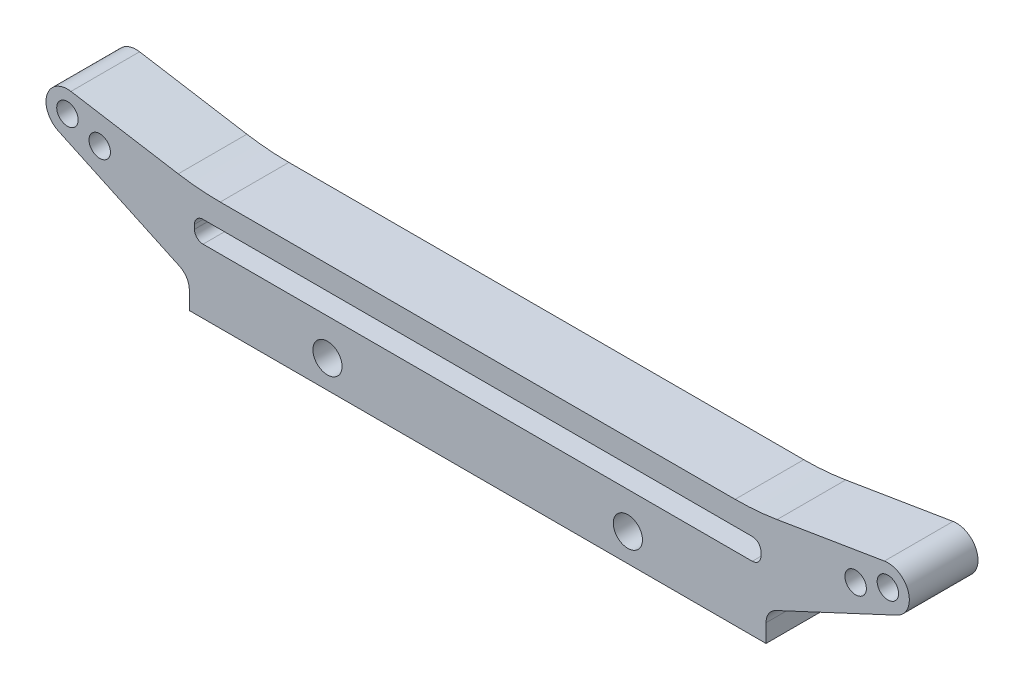
SolidWorks part; units mm, degrees
ref_plane "Front Plane" through (0, 0, 0) normal (0, 0, 1) x (1, 0, 0)
ref_plane "Top Plane" through (0, 0, 0) normal (0, 1, 0) x (1, 0, 0)
ref_plane "Right Plane" through (0, 0, 0) normal (1, 0, 0) x (0, 0, -1)
sketch "Sketch1" plane through (0, 0, 0) normal (0, 0, 1) x (1, 0, 0)
  line L0 (-33.6, 0) -> (33.6, 0)
  line L1 (-34.7548, 4.1585) -> (-48.8565, 10.7342)
  line L2 (-47.3925, 15.4666) -> (-34.8896, 13.4011)
  line L3 (33, 8.75) -> (33, 9.25)
  line L4 (0, -1.6163) -> (0, 13) construction
  line L5 (32, 7.75) -> (-32, 7.75)
  line L6 (47.3925, 15.4666) -> (34.8896, 13.4011)
  line L7 (-32, 10.25) -> (32, 10.25)
  line L8 (-30, 13) -> (30, 13)
  line L9 (-33, 8.75) -> (-33, 9.25)
  line L10 (34.7548, 4.1585) -> (48.8565, 10.7342)
  line L11 (-47.8, 13) -> (-36.9266, 9.0424) construction
  line L12 (-33.6, 0) -> (-33.6, 2.3458)
  line L13 (33.6, 0) -> (33.6, 2.3458)
  arc A0 (-47.3925, 15.4666) -> (-48.8565, 10.7342) centre (-47.8, 13) ccw
  arc A1 (-34.8896, 13.4011) -> (-30, 13) centre (-30, 43) ccw
  arc A2 (-34.7548, 4.1585) -> (-33.6, 2.3458) centre (-35.6, 2.3458) cw
  arc A3 (-32, 10.25) -> (-33, 9.25) centre (-32, 9.25) ccw
  arc A4 (-32, 7.75) -> (-33, 8.75) centre (-32, 8.75) cw
  arc A5 (32, 7.75) -> (33, 8.75) centre (32, 8.75) ccw
  arc A6 (32, 10.25) -> (33, 9.25) centre (32, 9.25) cw
  arc A7 (34.7548, 4.1585) -> (33.6, 2.3458) centre (35.6, 2.3458) ccw
  arc A8 (34.8896, 13.4011) -> (30, 13) centre (30, 43) cw
  arc A9 (47.3925, 15.4666) -> (48.8565, 10.7342) centre (47.8, 13) cw
  circle A10 centre (-47.8, 13) radius 0.5
  circle A11 centre (47.8, 13) radius 0.5
  circle A12 centre (-44.0412, 11.6319) radius 0.5
  circle A13 centre (44.0412, 11.6319) radius 0.5
  point P8 (0, 0)
  point P11 (0, 7.75)
  point P14 (0, 0)
  point P27 (0, 7.75)
  point P43 (0, 10.25)
  point P46 (-33.6, 3.62)
  point P48 (33.6, 3.62)
  dimension "D6" = 2.5
  dimension "D1" = 2.5
  dimension "D8" = 30
  dimension "D11" = 1
  dimension "D12" = 1
  dimension "D14" = 4
  dimension "D15" = 1
  dimension "D9" = 2
  dimension "D17" = 2
  dimension "D2" = 25
  dimension "D3" = 13
  dimension "D4" = 7.75
  dimension "D5" = 47.8
  dimension "D7" = 33
  dimension "D10" = 30
  dimension "D13" = 20
  dimension "D16" = 33.6
extrude "Boss-Extrude1" add sketch "Sketch1" along normal blind 8
hole_wizard "M3 Clearance Hole1" positions "Sketch4" profile "Sketch5" hole size "M3" standard "ANSI Metric" end condition through all
sketch "Sketch4" plane through (0, 0, 8) normal (0, 0, 1) x (1, 0, 0)
  line L0 (0, 10.7095) -> (0, -12.2541) construction
  line L3 (-33.6, 0) -> (33.6, 0) construction
  point P0 (-17.5, 3.5)
  point P2 (17.5, 3.5)
  dimension "D1" = 17.5
  dimension "D2" = 35
  dimension "D3" = 3.5
sketch "Sketch5" plane through (-17.5, 3.5, 8) normal (1, 0, 0) x (0, -1, 0)
  line L0 (0, 0) -> (0, 8)
  line L1 (0, 8) -> (1.7, 8)
  line L2 (1.7, 8) -> (1.7, 0)
  line L5 (1.7, 0) -> (0, 0)
  line L11 (0, -6.35) -> (0, 107.95) construction
  dimension "Thru Hole Dia." = 3.4
  dimension "Thru Hole Depth" = 8
hole_wizard "M3x0.5 Tapped Hole1" positions "Sketch2" profile "Sketch3" tap size "M3x0.5" standard "ANSI Metric" end condition through all
sketch "Sketch2" plane through (0, 0, 8) normal (0, 0, 1) x (1, 0, 0)
  point P14 (-47.8, 13)
  point P17 (47.8, 13)
  point P21 (-44.0412, 11.6319)
  point P24 (44.0412, 11.6319)
sketch "Sketch3" plane through (-47.8, 13, 8) normal (1, 0, 0) x (0, -1, 0)
  line L0 (0, 0) -> (0, 8)
  line L1 (0, 8) -> (1.25, 8)
  line L2 (1.25, 8) -> (1.25, 0)
  line L5 (1.25, 0) -> (0, 0)
  line L11 (0, -6.35) -> (0, 107.95) construction
  dimension "Thru Tap Drill Dia." = 2.5
  dimension "Thru Tap Drill Depth" = 8
cosmetic thread "Hole Thread1" parameters "D2"=3
cosmetic thread "Hole Thread2" parameters "D2"=3
cosmetic thread "Hole Thread3" parameters "D2"=3
cosmetic thread "Hole Thread4" parameters "D2"=3
sketch "Sketch6" plane through (0, 0, 0) normal (0, -1, 0) x (1, 0, 0)
  line L1 (-33.6, 0) -> (33.6, 0)
  line L2 (-33.6, 0) -> (-33.6, 8)
  line L3 (-33.6, 8) -> (33.6, 8)
  line L4 (33.6, 0) -> (33.6, 8)
extrude "Cut-Extrude1" cut sketch "Sketch6" against normal blind 0.25
